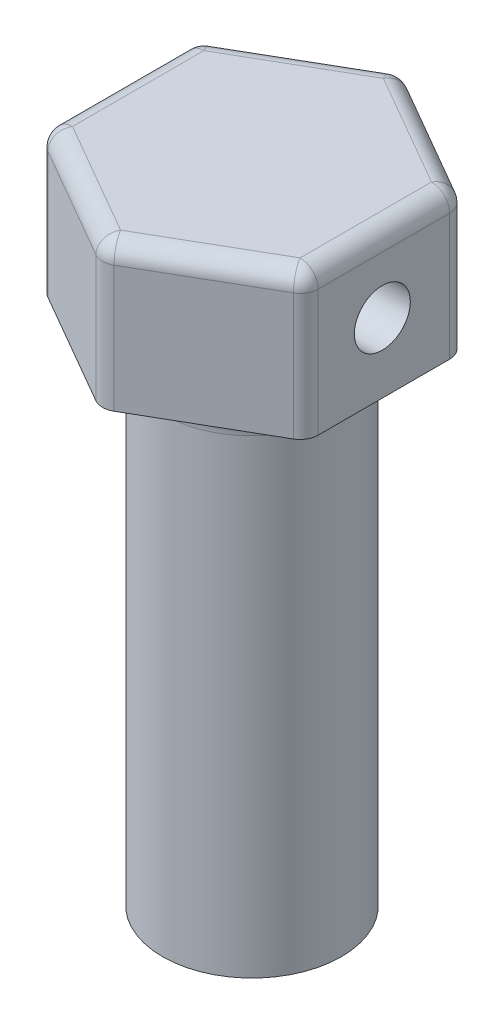
SolidWorks part; units mm, degrees
ref_plane "Front Plane" through (0, 0, 0) normal (0, 0, 1) x (1, 0, 0)
ref_plane "Top Plane" through (0, 0, 0) normal (0, 1, 0) x (1, 0, 0)
ref_plane "Right Plane" through (0, 0, 0) normal (1, 0, 0) x (0, 0, -1)
sketch "Sketch1" plane through (0, 0, 0) normal (0, 1, 0) x (1, 0, 0)
  line L1 (7.3, -4.2147) -> (7.3, 4.2147)
  line L2 (7.3, 4.2147) -> (0, 8.4293)
  line L3 (0, 8.4293) -> (-7.3, 4.2147)
  line L4 (-7.3, 4.2147) -> (-7.3, -4.2147)
  line L5 (-7.3, -4.2147) -> (0, -8.4293)
  line L6 (0, -8.4293) -> (7.3, -4.2147)
  circle A0 centre (0, 0) radius 7.3 construction
  dimension "D1" = 14.6
extrude "Boss-Extrude1" add sketch "Sketch1" along normal blind 8
sketch "Sketch2" plane through (0, 0, 0) normal (0, -1, 0) x (1, 0, 0)
  line L0 (-1.55, 1.3416) -> (-1.55, -1.3416)
  line L1 (-7.3, -4.2147) -> (-7.3, 4.2147) construction
  arc A0 (-1.55, -1.3416) -> (-1.55, 1.3416) centre (0, 0) ccw
  circle A1 centre (0, 0) radius 4.95
  dimension "D1" = 4.1
  dimension "D2" = 9.9
  dimension "D3" = 1.55
extrude "Boss-Extrude2" add sketch "Sketch2" along normal blind 28 contours A1 | A0 L0
fillet "Fillet1" radius 2 1 edges at (0, 0, 4.95)
sketch "Sketch3" plane through (7.3, 0, 0) normal (1, 0, 0) x (0, 0, -1)
  line L0 (-6.95, 0) -> (6.95, 0) construction
  line L1 (4.2147, 8) -> (4.2147, 0) construction
  circle A0 centre (-0.0853, 3.85) radius 1.55
  dimension "D1" = 3.1
  dimension "D2" = 3.85
  dimension "D3" = 4.3
extrude "Cut-Extrude1" cut sketch "Sketch3" against normal through all
fillet "Fillet2" radius 1 12 edges at (-3.65, 8, 6.322) (-7.3, 8, 0) (-3.65, 8, -6.322) (3.65, 8, -6.322) (7.3, 8, 0) (3.65, 8, 6.322) (-7.3, 4, -4.2147) (0, 4, -8.4293) (7.3, 4, -4.2147) (7.3, 4, 4.2147) (0, 4, 8.4293) (-7.3, 4, 4.2147)
sketch "Sketch4" plane through (0, 0, 0) normal (1, 0, 0) x (0, 0, -1)
  line L1 (-16.1086, 1.5942) -> (18.1695, 1.5942)
  line L2 (-16.1086, 1.5942) -> (-16.1086, -34.824)
  line L3 (-16.1086, -34.824) -> (18.1695, -34.824)
  line L4 (18.1695, 1.5942) -> (18.1695, -34.824)
extrude "Cut-Extrude2" [suppressed] cut sketch "Sketch4" against normal through all both and the other way through all
sketch "Sketch5" plane through (0, -28, 0) normal (0, -1, 0) x (1, 0, 0)
  circle A0 centre (0, 0) radius 2.05
  dimension "D1" = 4.1
extrude "Cut-Extrude3" cut sketch "Sketch5" against normal blind 4
equation "\"1.ø15\"=1.5"
